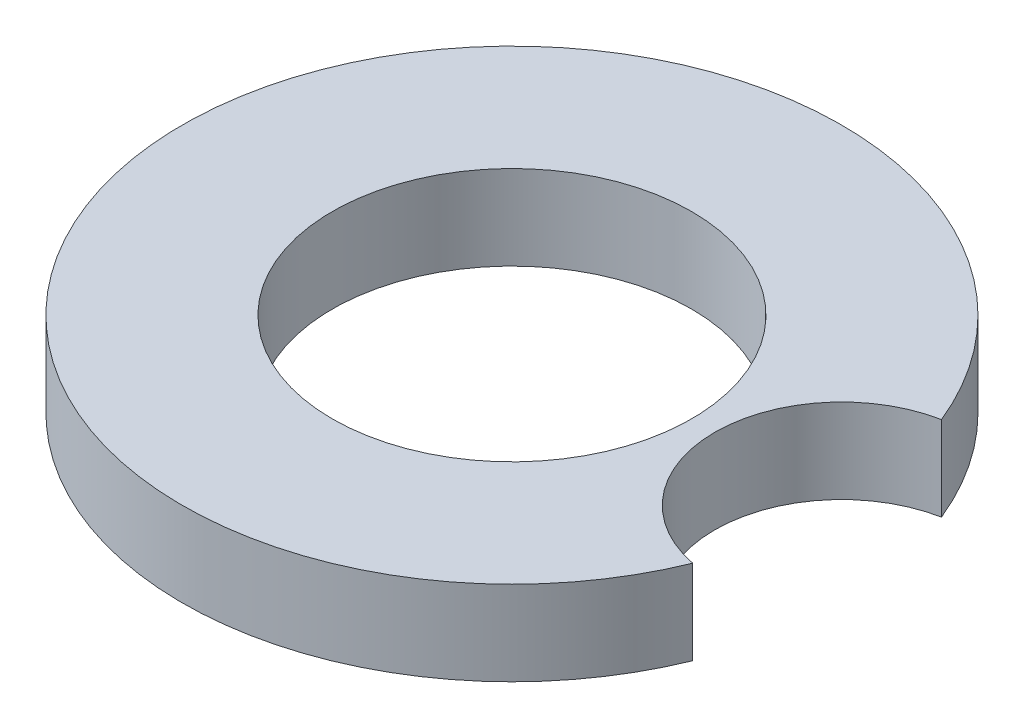
SolidWorks part; units mm, degrees
ref_plane "Front Plane" through (0, 0, 0) normal (0, 0, 1) x (1, 0, 0)
ref_plane "Top Plane" through (0, 0, 0) normal (0, 1, 0) x (1, 0, 0)
ref_plane "Right Plane" through (0, 0, 0) normal (1, 0, 0) x (0, 0, -1)
sketch "Sketch1" plane through (0, 0, 0) normal (0, 1, 0) x (1, 0, 0)
  circle A0 centre (0, 0) radius 27
  circle A1 centre (0, 0) radius 49.53
  dimension "Front_CR_ID" = 54
  dimension "Front_CR_OD" = 99.06
extrude "Boss-Extrude1" add sketch "Sketch1" along normal blind 12.7 contours A1
extrude "Cut-Extrude2" cut sketch "Sketch1<10>" along normal through all contours A0
sketch "Sketch1<10>" plane through (0, 0, 0) normal (0, 1, 0) x (1, 0, 0) same geometry as "Sketch1"
sketch "Sketch2" plane through (0, 12.7, 0) normal (0, 1, 0) x (1, 0, 0)
  circle A2 centre (49.53, 0) radius 19.05
  circle A3 centre (0, 0) radius 49.53 construction
  dimension "D1" = 38.1
extrude "Cut-Extrude3" cut sketch "Sketch2" against normal through all contours A2
ref_plane "Plane1" through (0, 6.35, 0) normal (0, -1, 0) x (-1, 0, 0)
equation "\"Motor_OD\"= 54mm"
equation "\"Aft_Section_Length\"= 30in"
equation "\"Mid_Coupler_Length\"= 12in"
equation "\"AB_Coupler_OD_Length\"= 1in"
equation "\"AB_Coupling_Section_Length\"= 0.375in"
equation "\"AB_Coupler_Length\"= \"AB_Coupler_OD_Length\" + \"AB_Coupling_Section_Length\" * 2"
equation "\"Cutout_Angle\"= 60"
equation "\"AB_Paddle_Height\"= 0.375in"
equation "\"AB_Coupler_Num_Screws\"= 4"
equation "\"Num_Cutouts\"= 4"
equation "\"AB_Coupler_OD\"= 4.024in"
equation "\"AB_Coupler_ID\"= 3.7in"
equation "\"AB_Coupler_Surface_Diameter\"= 3.899in"
equation "\"AB_Coupling_Screw_Diameter\"= 0.1065in"
equation "\"AB_Central_Bushing_Length\"= 0.75in"
equation "\"Lead_Screw_Dist\"= 2in"
equation "\"Lead_Screw_Diam\"= 0.375in"
equation "\"Lead_Screw_Length\"= \"Mid_Coupler_Length\" + 2*0.375in + 2*0.5in"
equation "\"Paddle_Pin_Offset\"= 0.25in"
equation "\"Paddle_Pin_Radius\"= 2.25*2/3in"
equation "\"Paddle_Gear_OD\"= 3.2in"
equation "\"Fwd_BKHD_From_Top\"= 18in"
equation "\"Front_CR_ID@Sketch1\"=\"Motor_OD\""
equation "\"Body_Tube_OD\"= 4.024in"
equation "\"Body_Tube_ID\"= 3.90in"
equation "\"Coupler_OD\"= 3.899in"
equation "\"Coupler_ID\"= 3.755in"
equation "\"Fwd_Section_Length\"= 25in"
equation "\"Mid_Section_Length\"= 6in"
equation "\"Aft_Upper_Tube_Length\"= 10in"
equation "\"Aft_Lower_Tube_Length\"= 18in"
equation "\"Nosecone_Coupler_Length\"= 5in"
equation "\"Avionics_Bulkhead_Thickness\"= 0.25in"
equation "\"Avionics_Bulkhead_Lip\"= 0.125in"
equation "\"Avionics_Board_Length\"= \"Mid_Coupler_Length\" - 2*\"Avionics_Bulkhead_Lip\""
equation "\"Lead_Screw_Hole_Diam\"= (27/64)*1in"
equation "\"Front_CR_OD@Sketch1\"=\"Body_Tube_ID\""
equation "\"Centering_Ring_Cutout_Dia\"=1.5in"
equation "\"D1@Sketch2\"=\"Centering_Ring_Cutout_Dia\""
